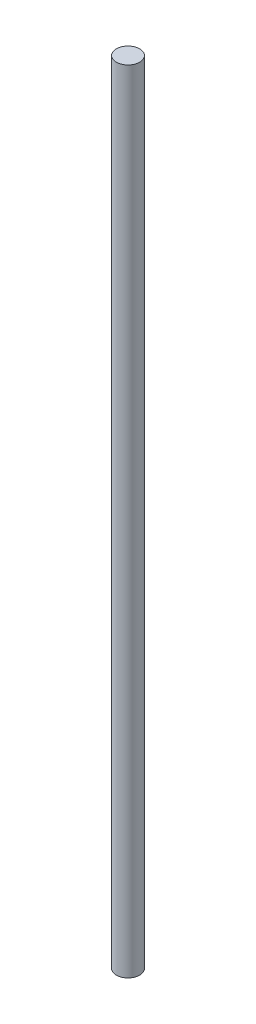
SolidWorks part; units mm, degrees
ref_plane "Front Plane" through (0, 0, 0) normal (0, 0, 1) x (1, 0, 0)
ref_plane "Top Plane" through (0, 0, 0) normal (0, 1, 0) x (1, 0, 0)
ref_plane "Right Plane" through (0, 0, 0) normal (1, 0, 0) x (0, 0, -1)
sketch "Sketch1" plane through (0, 0, 0) normal (0, 1, 0) x (1, 0, 0)
  circle A0 centre (0, 0) radius 2.5
  dimension "D1" = 5
extrude "Boss-Extrude1" add sketch "Sketch1" along normal offset from surface (170 mm away) 10 offset beyond the face yes
